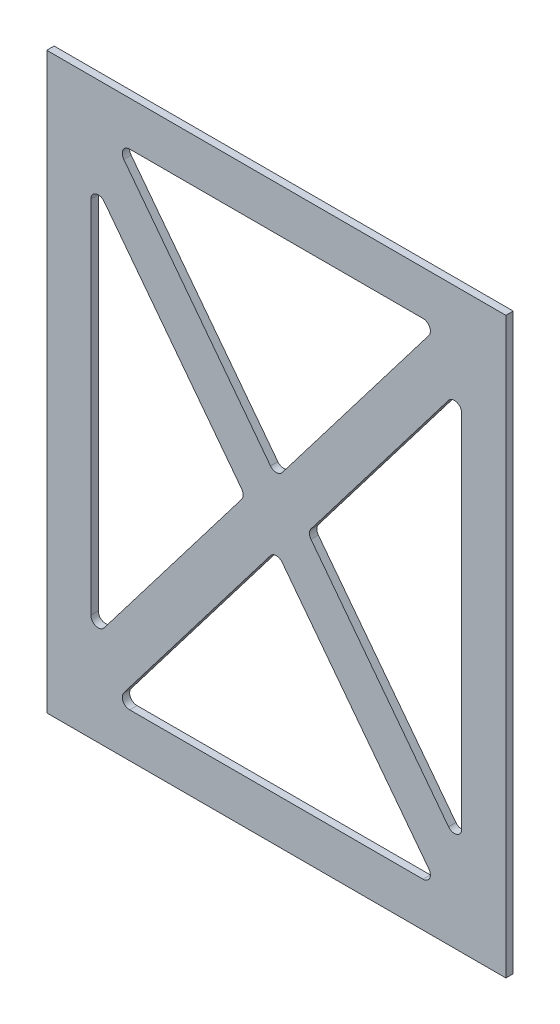
SolidWorks part; units mm, degrees
ref_plane "Front Plane" through (0, 0, 0) normal (0, 0, 1) x (1, 0, 0)
ref_plane "Top Plane" through (0, 0, 0) normal (0, 1, 0) x (1, 0, 0)
ref_plane "Right Plane" through (0, 0, 0) normal (1, 0, 0) x (0, 0, -1)
sketch "Sketch1" plane through (0, 0, 0) normal (0, 0, 1) x (1, 0, 0)
  line L1 (-99.06, -123.825) -> (99.06, -123.825)
  line L2 (-99.06, -123.825) -> (-99.06, 123.825)
  line L3 (-99.06, 123.825) -> (99.06, 123.825)
  line L4 (99.06, -123.825) -> (99.06, 123.825)
  line L5 (-99.06, -123.825) -> (99.06, 123.825) construction
  line L6 (-99.06, 123.825) -> (99.06, -123.825) construction
  point P0 (0, 0)
  dimension "D1" = 198.12
  dimension "D2" = 247.65
extrude "Boss-Extrude1" add sketch "Sketch1" along normal blind 3.175
sketch "Sketch2" plane through (0, 0, 3.175) normal (0, 0, 1) x (1, 0, 0)
  line L0 (0, 13.4704) -> (-69.7235, 104.775)
  line L1 (-80.01, -104.775) -> (80.01, -104.775)
  line L2 (-80.01, -104.775) -> (-80.01, 104.775)
  line L3 (-80.01, 104.775) -> (80.01, 104.775)
  line L4 (99.06, -123.825) -> (99.06, 123.825)
  line L5 (99.06, 123.825) -> (-99.06, 123.825)
  line L6 (-99.06, 123.825) -> (-99.06, -123.825)
  line L7 (-99.06, -123.825) -> (99.06, -123.825)
  line L8 (99.06, -123.825) -> (99.06, 123.825)
  line L9 (99.06, 123.825) -> (-99.06, 123.825)
  line L10 (-99.06, 123.825) -> (-99.06, -123.825)
  line L11 (-99.06, -123.825) -> (99.06, -123.825)
  line L12 (80.01, -104.775) -> (80.01, 104.775)
  line L13 (-80.01, -104.775) -> (80.01, 104.775) construction
  line L14 (-80.01, 104.775) -> (80.01, -104.775) construction
  line L15 (0, 13.4704) -> (69.7235, 104.775)
  line L16 (-13.4704, 0) -> (-80.01, 87.1352)
  line L17 (-13.4704, 0) -> (-80.01, -87.1352)
  line L18 (13.4704, 0) -> (80.01, 87.1352)
  line L19 (0, 13.4704) -> (-13.4704, 0)
  line L20 (-13.4704, 0) -> (0, -13.4704)
  line L21 (0, -13.4704) -> (13.4704, 0)
  line L22 (13.4704, 0) -> (0, 13.4704)
  line L23 (13.4704, 0) -> (80.01, -87.1352)
  line L24 (0, -13.4704) -> (69.7235, -104.775)
  line L25 (0, -13.4704) -> (-69.7235, -104.775)
  circle A0 centre (0, 0) radius 9.525 construction
  point P2 (0, 0)
  dimension "D2" = 19.05
  dimension "D3" = 19.05
  dimension "D4" = 19.05
  dimension "D1" = 0
extrude "Cut-Extrude1" cut sketch "Sketch2" against normal up to next contours L17 L16 L2 | L0 L15 L3 | L18 L23 L12 | L24 L25 L1 region at (0, 74.3401, 3.175) region at (-57.8301, 0, 3.175) region at (57.8301, 0, 3.175) region at (0, -74.3401, 3.175)
fillet "Fillet1" radius 3.175 12 edges at (80.01, -87.1352, 1.5875) (69.7235, -104.775, 1.5875) (-69.7235, -104.775, 1.5875) (-80.01, -87.1352, 1.5875) (-80.01, 87.1352, 1.5875) (13.4704, 0, 1.5875) (0, -13.4704, 1.5875) (-13.4704, 0, 1.5875) (0, 13.4704, 1.5875) (69.7235, 104.775, 1.5875) (80.01, 87.1352, 1.5875) (-69.7235, 104.775, 1.5875)
